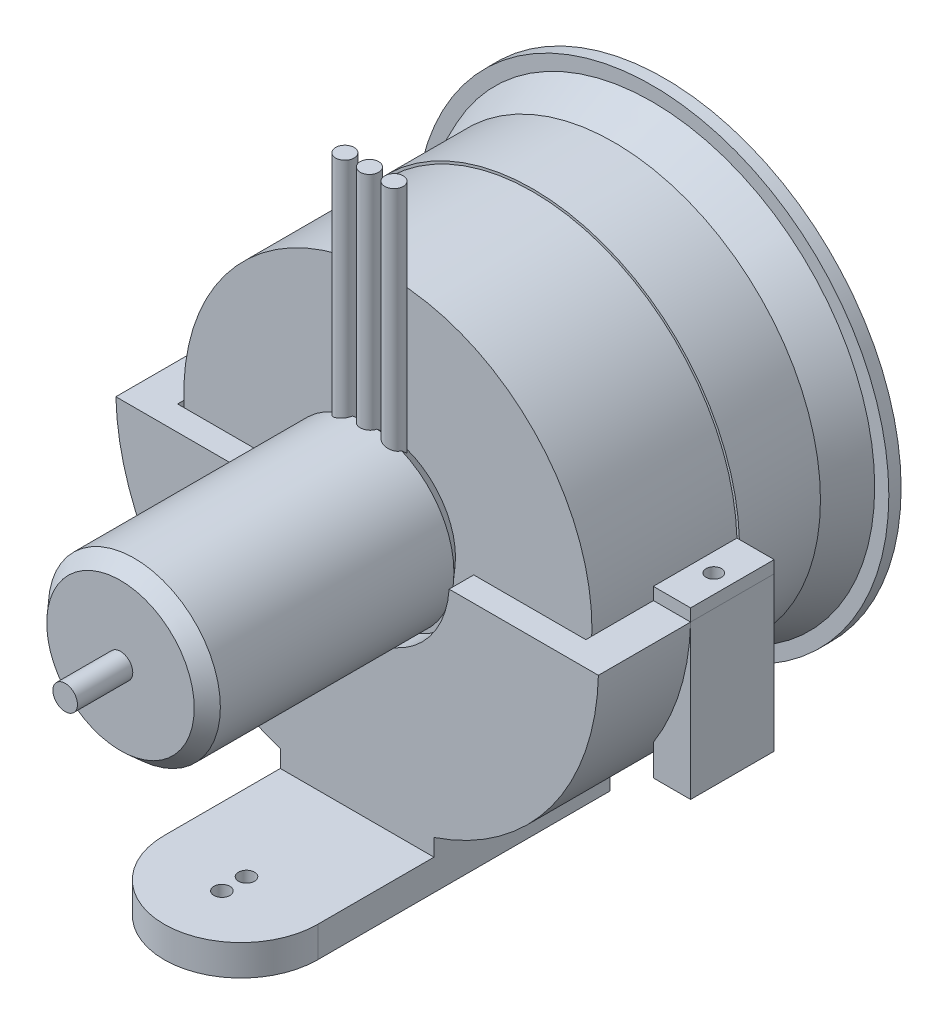
SolidWorks part; units mm, degrees
ref_plane "Front Plane" through (0, 0, 0) normal (1, 0, 0) x (0, 1, 0)
ref_plane "Top Plane" through (0, 0, 0) normal (0, 0, 1) x (0, 1, 0)
ref_plane "Right Plane" through (0, 0, 0) normal (0, 1, 0) x (-1, 0, 0)
sketch "Sketch1" plane through (0, 0, 0) normal (1, 0, 0) x (0, 1, 0)
  line L0 (0, 0) -> (0, -32.442) construction
  line L1 (0, 0) -> (38.5, 0)
  line L2 (38.5, 0) -> (38.5, 2)
  line L3 (38.5, 2) -> (36.2, 2)
  line L4 (36.2, 2) -> (33.6, 8.225)
  line L5 (33.6, 8.225) -> (33.6, 21.4)
  line L6 (33.2, 21.4) -> (33.2, 45)
  line L7 (33.2, 45) -> (5, 45)
  line L9 (5, 46) -> (12, 46)
  line L10 (12, 46) -> (14, 48.25)
  line L11 (14, 48.25) -> (14, 86.25)
  line L12 (14, 86.25) -> (12, 88.5)
  line L13 (12, 88.5) -> (2, 88.5)
  line L14 (2, 88.5) -> (2, 97.5)
  line L15 (2, 97.5) -> (0, 97.5)
  line L17 (33.2, 21.4) -> (33.6, 21.4)
  line L19 (0, 97.5) -> (0, 0)
  line L20 (5, 46) -> (5, 45)
  dimension "D1" = 77
  dimension "D2" = 72.4
  dimension "D3" = 67.2
  dimension "D4" = 66.4
  dimension "D5" = 45
  dimension "D6" = 23.6
  dimension "D7" = 97.5
  dimension "D8" = 2
  dimension "D9" = 4
  dimension "D10" = 28
  dimension "D11" = 1
  dimension "D12" = 42.5
  dimension "D13" = 10
  dimension "D14" = 10
  dimension "D15" = 38
revolve "Revolve1" add sketch "Sketch1" angle 360 about L0
sketch "Sketch3" plane through (0, 0, 0) normal (1, 0, 0) x (0, 1, 0)
  line L0 (33.2, 45) -> (-33.2, 45) construction
  line L1 (-1, 35) -> (1, 35)
  line L2 (-1, 35) -> (-1, 21.4)
  line L3 (-1, 21.4) -> (1, 21.4)
  line L4 (1, 35) -> (1, 21.4)
  point P4 (0, 21.4)
  dimension "D1" = 13.6
  dimension "D2" = 10
  dimension "D3" = 2
extrude "Boss-Extrude1" add sketch "Sketch3" along normal mid plane 78.5
sketch "Sketch4" plane through (0, 1, 0) normal (0, 1, 0) x (-1, 0, 0)
  line L0 (-39.25, 35) -> (-33.1849, 35) construction
  line L1 (-39.25, 28.2) -> (-33.1849, 28.2) construction
  line L4 (-39.25, 21.4) -> (-39.25, 35) construction
  line L5 (-33.1849, 21.4) -> (-33.1849, 35) construction
  circle A0 centre (-36.2175, 28.2) radius 1.25
  dimension "D2" = 2.5
  dimension "D1" = 6.8
extrude "Cut-Extrude1" cut sketch "Sketch4" against normal through all
mirror "Mirror1" about plane through (0, 0, 0) normal (1, 0, 0) of "Cut-Extrude1"
sketch "Sketch5" plane through (0, 0, 0) normal (0, 1, 0) x (-1, 0, 0)
  line L2 (-12, 46) -> (12, 46) construction
  circle A0 centre (0, 48) radius 1.5
  circle A1 centre (4, 48) radius 1.5
  circle A2 centre (-4, 48) radius 1.5
  dimension "D1" = 3
  dimension "D2" = 0.5
  dimension "D3" = 1
  dimension "D4" = 1
extrude "Boss-Extrude5" add sketch "Sketch5" along normal blind 50
sketch "Sketch6" plane through (0, 0, 45) normal (0, 0, 1) x (1, 0, 0)
  line L0 (39.25, -1) -> (33.1849, -1)
  line L1 (-39.25, -1) -> (-33.2049, -1)
  line L2 (-39.25, -1) -> (-39.25, -26)
  line L3 (-39.25, -26) -> (-33.2049, -26)
  line L4 (-33.2049, -26) -> (-33.2049, -20.9522)
  line L5 (39.25, -1) -> (39.25, -26)
  line L6 (39.25, -26) -> (33.1849, -26)
  line L7 (33.1849, -26) -> (33.1849, -20.9839)
  arc A0 (-33.2049, -1) -> (33.2049, -1) centre (0, 0) ccw
  arc A1 (-39.25, -1) -> (39.25, -1) centre (0, 0) ccw
  circle A2 centre (0, 0) radius 33.2 construction
  point P19 (0, 0)
  dimension "D1" = 0.02
  dimension "D2" = 25
extrude "Boss-Extrude6" add sketch "Sketch6" against normal up to surface (23.6 mm away) and the other way blind 5 separate body contours L1 A1 L0 A0 region at (36.7349, -11.149, 45) up to face at (-36.4213, 0, 21.4)
extrude "Boss-Extrude7" add sketch "Sketch6<4>" along normal up to surface (-10 mm away) from surface contours A1 L7 L6 L5 | A1 L2 L3 L4 region at (36.9268, -19.1147, 45) region at (-36.932, -19.1085, 45) up to face at (36.2212, 0, 35) starting at face at (36.4213, 0, 21.4)
sketch "Sketch6<4>" plane through (0, 0, 45) normal (0, 0, 1) x (1, 0, 0) same geometry as "Sketch6"
sketch "Sketch7" plane through (0, -26, 0) normal (0, -1, 0) x (1, 0, 0)
  circle A0 centre (-36.2175, 28.2) radius 1.25 construction
  circle A1 centre (-36.2175, 28.2) radius 1.25
extrude "Cut-Extrude2" cut sketch "Sketch7" against normal through all
mirror "Mirror2" about plane through (0, 0, 0) normal (1, 0, 0) of "Cut-Extrude2"
sketch "Sketch8" plane through (0, 0, 50) normal (0, 0, 1) x (1, 0, 0)
  line L0 (-33.2049, -1) -> (-14.9666, -1)
  line L1 (33.2049, -1) -> (14.9666, -1)
  circle A0 centre (0, 0) radius 14 construction
  circle A1 centre (0, 0) radius 14 construction
  arc A2 (-14.9666, -1) -> (14.9666, -1) centre (0, 0) ccw
  circle A3 centre (0, 0) radius 15 construction
  arc A4 (-33.2049, -1) -> (33.2049, -1) centre (0, 0) ccw construction
  arc A5 (-33.2049, -1) -> (33.2049, -1) centre (0, 0) ccw
  point P8 (0, 0)
  point P9 (0, 0)
  point P10 (0, 0)
  point P11 (-18.0354, -1)
  point P12 (18.2998, -1)
  point P16 (-14.9666, -1)
  point P17 (14.9666, -1)
  dimension "D1" = 1
extrude "Boss-Extrude8" add sketch "Sketch8" against normal offset from surface (4 mm away) 1 up to face at (5, 0, 45)
ref_plane "Plane1" through (0, -45, 0) normal (0, -1, 0) x (1, 0, 0)
sketch "Sketch9" plane through (0, -45, 0) normal (0, -1, 0) x (1, 0, 0)
  line L0 (-33.2049, 21.4) -> (33.1849, 21.4) construction
  line L1 (-12.5, 81.4) -> (12.5, 81.4)
  line L2 (-12.5, 81.4) -> (-12.5, 21.4)
  line L3 (-12.5, 21.4) -> (12.5, 21.4)
  line L4 (12.5, 81.4) -> (12.5, 21.4)
  line L5 (4, 61.4257) -> (4, 72) construction
  line L6 (-4, 72) -> (-4, 61.4257) construction
  line L7 (4, 61.4257) -> (4, 72) construction
  line L8 (-4, 72) -> (-4, 61.4257) construction
  line L9 (4.05, 61.4257) -> (4.05, 72)
  line L10 (-4.05, 72) -> (-4.05, 61.4257)
  arc A0 (0, 38.025) -> (0, 57.975) centre (0, 48) ccw construction
  arc A1 (4, 61.4257) -> (5.15, 54.7416) centre (24, 61.4257) ccw construction
  arc A2 (4, 72) -> (-4, 72) centre (0, 72) ccw construction
  arc A3 (-5.15, 54.7416) -> (-4, 61.4257) centre (-24, 61.4257) ccw construction
  arc A4 (0, 57.975) -> (0, 38.025) centre (0, 48) ccw construction
  arc A5 (0, 38.025) -> (4.5207, 56.8918) centre (0, 48) ccw construction
  arc A6 (4, 61.4257) -> (4.5207, 56.8918) centre (24, 61.4257) ccw construction
  arc A7 (4, 72) -> (-4, 72) centre (0, 72) ccw construction
  arc A8 (-4.5207, 56.8918) -> (-4, 61.4257) centre (-24, 61.4257) ccw construction
  arc A9 (-4.5207, 56.8918) -> (0, 38.025) centre (0, 48) ccw construction
  arc A10 (4.05, 72) -> (-4.05, 72) centre (0, 72) ccw
  arc A11 (-4.5641, 56.9258) -> (-4.05, 61.4257) centre (-24, 61.4257) ccw
  arc A12 (-4.5641, 56.9258) -> (0, 37.975) centre (0, 48) ccw
  arc A13 (0, 37.975) -> (4.5641, 56.9258) centre (0, 48) ccw
  arc A14 (4.05, 61.4257) -> (4.5641, 56.9258) centre (24, 61.4257) ccw
  point P6 (0, 21.4)
  dimension "D1" = 60
  dimension "D2" = 25
  dimension "D3" = 0.05
extrude "Boss-Extrude9" add sketch "Sketch9" against normal blind 5 separate body contours A14 L9 A10 L10 A11 A12 A13 | L4 L1 L2 L3 L9 A14 A13 A12 A11 L10 A10 region at (0, -45, 80.75) region at (0, -45, 53.7265)
extrude "Cut-Extrude3" cut sketch "Sketch9<3>" against normal blind 3 contours A14 L9 A10 L10 A11 A12 A13 region at (0, -45, 53.7265)
sketch "Sketch9<3>" plane through (0, -45, 0) normal (0, -1, 0) x (1, 0, 0) same geometry as "Sketch9"
sketch "Sketch10" plane through (0, -40, 0) normal (0, 1, 0) x (-1, 0, 0)
  line L0 (39.25, 50) -> (-39.25, 50) construction
  line L1 (-12.5, 50) -> (12.5, 50)
  line L2 (-12.5, 50) -> (-12.5, 21.4)
  line L3 (-12.5, 21.4) -> (12.5, 21.4)
  line L4 (12.5, 50) -> (12.5, 21.4)
  line L5 (-33.1849, 21.4) -> (33.2049, 21.4) construction
  line L6 (12.5, 81.4) -> (12.5, 21.4) construction
  line L7 (-12.5, 81.4) -> (-12.5, 21.4) construction
extrude "Boss-Extrude10" add sketch "Sketch10" along normal up to surface (2.7802 mm away) up to face at (-0.0055, -18.1561, 35.35)
sketch "Sketch11" plane through (0, -40, 0) normal (0, 1, 0) x (1, 0, 0)
  arc A0 (0, -69.3) -> (0, -66.7) centre (0, -68) ccw construction
  arc A1 (0, -66.7) -> (0, -69.3) centre (0, -68) ccw construction
  arc A2 (0, -73.3) -> (0, -70.7) centre (0, -72) ccw construction
  arc A3 (0, -70.7) -> (0, -73.3) centre (0, -72) ccw construction
  arc A4 (0, -69.3) -> (0, -66.7) centre (0, -68) ccw
  arc A5 (0, -66.7) -> (0, -69.3) centre (0, -68) ccw
  arc A6 (0, -73.3) -> (0, -70.7) centre (0, -72) ccw
  arc A7 (0, -70.7) -> (0, -73.3) centre (0, -72) ccw
extrude "Cut-Extrude4" cut sketch "Sketch11" against normal through all
fillet "Fillet1" 2 edges at (-12.5, -42.5, 81.4) (12.5, -42.5, 81.4) type full round first side face at (-12.5, -40.7399, 50.9333) second side face at (12.5, -40.7399, 50.9333) middle face at (0, -42.5, 81.4)
